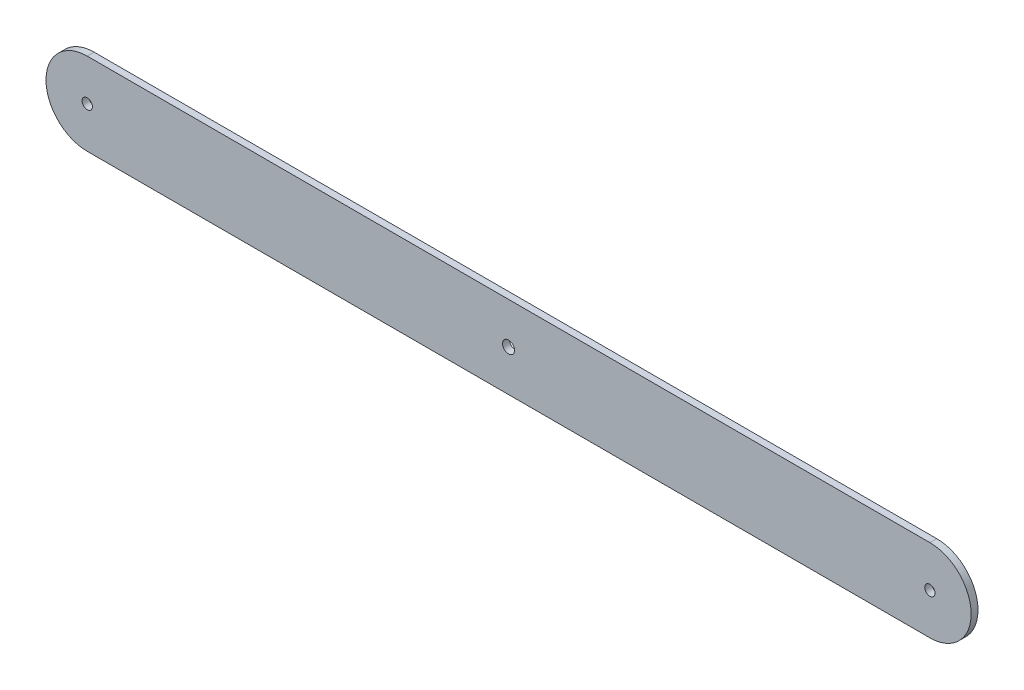
SolidWorks part; units mm, degrees
material "6061-T6 (SS)"
ref_plane "Front Plane" through (0, 0, 0) normal (0, 0, 1) x (1, 0, 0)
ref_plane "Top Plane" through (0, 0, 0) normal (0, 1, 0) x (1, 0, 0)
ref_plane "Right Plane" through (0, 0, 0) normal (1, 0, 0) x (0, 0, -1)
ref_axis "X" through (-88.99, 0, 0) along (1, 0, 0)
ref_axis "Y" through (0, 55, 0) along (0, -1, 0)
ref_axis "Z" through (0, 0, -88.99) along (0, 0, 1)
sketch "Sketch1" plane through (0, 0, 0) normal (0, 0, 1) x (1, 0, 0)
  line L0 (-122.6, 0) -> (122.6, 0) construction
  line L1 (-122.6, 12) -> (122.6, 12)
  line L2 (-122.6, -12) -> (122.6, -12)
  line L4 (-32.5, 12) -> (32.5, 12) construction
  arc A0 (-122.6, 12) -> (-122.6, -12) centre (-122.6, 0) ccw
  arc A1 (122.6, -12) -> (122.6, 12) centre (122.6, 0) ccw
  circle A2 centre (-122.6, 0) radius 1.5
  circle A3 centre (0, 0) radius 1.75
  circle A4 centre (122.6, 0) radius 1.5
  circle A5 centre (-122.6, 0) radius 1.5 construction
  circle A6 centre (0, 0) radius 1.75 construction
  point P2 (0, 0)
extrude "Boss-Extrude1" add sketch "Sketch1" along normal blind 2
